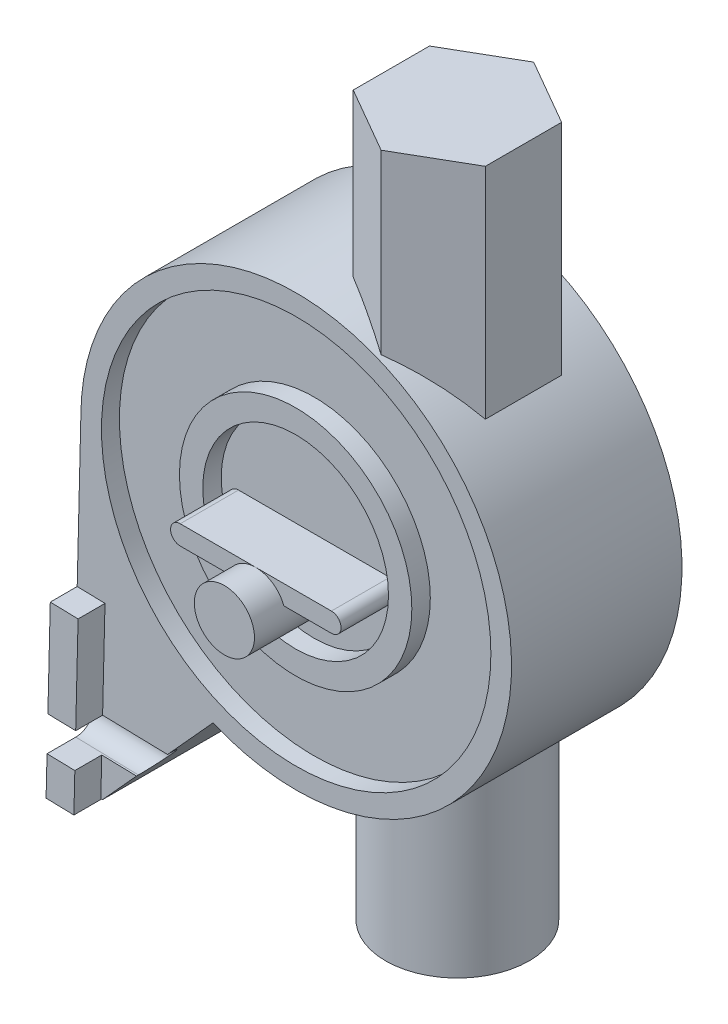
SolidWorks part; units mm, degrees
ref_plane "Front Plane" through (0, 0, 0) normal (0, 0, 1) x (1, 0, 0)
ref_plane "Top Plane" through (0, 0, 0) normal (0, 1, 0) x (1, 0, 0)
ref_plane "Right Plane" through (0, 0, 0) normal (1, 0, 0) x (0, 0, -1)
sketch "Sketch1" plane through (0, 0, 0) normal (0, 0, 1) x (1, 0, 0)
  line L0 (254.309, 185.0586) -> (255.9795, 135.0866) construction
  dimension "D1" = 50
sketch "Sketch3" plane through (0, 0, 0) normal (0, 0, 1) x (1, 0, 0)
  circle A0 centre (225, 142.5) radius 24
  dimension "D1" = 48
extrude "Boss-Extrude1" add sketch "Sketch3" along normal blind 19
sketch "Sketch5" plane through (0, 0, 0) normal (0, 0, 1) x (1, 0, 0)
  line L0 (201, 142.5) -> (200.1276, 106.7852)
  line L1 (200.1276, 106.7852) -> (203.4142, 106.7852)
  line L2 (203.4142, 106.7852) -> (215.7335, 120.3611)
  circle A0 centre (225, 142.5) radius 24 construction
  circle A3 centre (225, 142.5) radius 24
  arc A4 (201, 142.5) -> (215.7335, 120.3611) centre (225, 142.5) ccw
  dimension "D1" = 0
extrude "Boss-Extrude2" add sketch "Sketch5" along normal blind 19
ref_plane "Plane1" through (0, 0, 10) normal (0, 0, 1) x (1, 0, 0)
sketch "Sketch6" plane through (0, 0, 10) normal (0, 0, 1) x (1, 0, 0)
  line L0 (233.1699, 185.1714) -> (234.7697, 100.2588) construction
ref_axis "Axis1" through (233.1699, 185.1714, 10) along (0.0188, -0.9998, 0)
ref_plane "Plane2" through (0, 118.5, 0) normal (0, -1, 0) x (-1, 0, 0)
ref_plane "Plane3" through (0, 128.5, 0) normal (0, -1, 0) x (-1, 0, 0)
sketch "Sketch7" plane through (0, 128.5, 0) normal (0, -1, 0) x (-1, 0, 0)
  line L0 (3534.2774, -10) -> (-4002.217, -10) construction
  circle A0 centre (-233.9698, -10) radius 8
  dimension "D1" = 16
extrude "Boss-Extrude3" add sketch "Sketch7" along normal blind 22.5
ref_plane "Plane4" through (0, 158.5, 0) normal (0, -1, 0) x (-1, 0, 0)
sketch "Sketch8" plane through (0, 158.5, 0) normal (0, -1, 0) x (-1, 0, 0)
  line L0 (3534.2774, -10) -> (-4002.217, -10) construction
  line L1 (-241.331, -5.75) -> (-241.331, -14.25)
  line L2 (-241.331, -14.25) -> (-233.9698, -18.5)
  line L3 (-233.9698, -18.5) -> (-226.6086, -14.25)
  line L4 (-226.6086, -14.25) -> (-226.6086, -5.75)
  line L5 (-226.6086, -5.75) -> (-233.9698, -1.5)
  line L6 (-233.9698, -1.5) -> (-241.331, -5.75)
  circle A0 centre (-233.9698, -10) radius 7.3612 construction
extrude "Boss-Extrude4" add sketch "Sketch8" against normal blind 26
sketch "Sketch9" plane through (197.4015, -4.8217, 0) normal (-0.9997, 0.0244, 0) x (0, 0, 1)
  line L0 (0, 147.3657) -> (0, 111.6402) construction
  line L1 (19, 111.6402) -> (22, 111.6402)
  line L2 (19, 111.6402) -> (19, 130.8102)
  line L3 (19, 130.8102) -> (22, 130.8102)
  line L4 (22, 111.6402) -> (22, 130.8102)
  dimension "D1" = 22
  dimension "D2" = 19.17
extrude "Boss-Extrude5" add sketch "Sketch9" against normal blind 3.1
sketch "Sketch10" plane through (197.4015, -4.8217, 0) normal (-0.9997, 0.0244, 0) x (0, 0, 1)
  line L0 (5.15, 117.9352) -> (5.15, 122.2677) construction
  line L1 (16.85, 117.9352) -> (16.85, 122.2677) construction
  line L2 (11, 127.8393) -> (11, 106.4652) construction
  line L3 (0, 147.3657) -> (0, 111.6402) construction
  line L4 (22, 111.6402) -> (22, 130.8102) construction
  line L5 (3.205, 115.9902) -> (18.795, 115.9902) construction
  line L6 (19, 111.6402) -> (0, 111.6402) construction
  line L9 (0, 147.3657) -> (0, 111.6402)
  line L10 (0, 119.8802) -> (0, 115.9902)
  line L11 (3.205, 119.8802) -> (0, 119.8802)
  line L12 (22, 111.6402) -> (22, 130.8102)
  line L13 (22, 115.9902) -> (22, 119.8802)
  line L14 (3.205, 115.9902) -> (0, 115.9902)
  line L15 (18.795, 119.8802) -> (22, 119.8802)
  line L16 (18.795, 115.9902) -> (22, 115.9902)
  line L17 (1.46, 143.5702) -> (1.46, 162.4606) construction
  line L18 (4.82, 143.5702) -> (4.82, 151.263) construction
  line L19 (0, 171.9517) -> (0, 123.9517) construction
  line L21 (3.14, 141.8902) -> (22, 141.8902) construction
  arc A0 (3.205, 115.9902) -> (3.205, 119.8802) centre (3.205, 117.9352) ccw
  arc A1 (18.795, 119.8802) -> (18.795, 115.9902) centre (18.795, 117.9352) ccw
  circle A2 centre (3.14, 143.5702) radius 1.68
  dimension "D3" = 3.89
  dimension "D6" = 3.36
  dimension "D1" = 11.7
  dimension "D2" = 4.35
  dimension "D7" = 1.46
  dimension "D8" = 30.25
  dimension "D4" = 0
  dimension "D5" = 0
extrude "Cut-Extrude1" cut sketch "Sketch10" against normal blind 15
sketch "Sketch11" plane through (0, 0, 19) normal (0, 0, 1) x (1, 0, 0)
  line L0 (194.6129, 166.5) -> (247.7386, 166.5) construction
  line L1 (225, 164.2) -> (190.9337, 164.2) construction
  arc A0 (215.7335, 120.3611) -> (201, 142.5) centre (225, 142.5) ccw construction
  circle A1 centre (225, 142.5) radius 21.7
  point P0 (225, 142.5)
  point P1 (225, 142.5)
  dimension "D1" = 2.3
extrude "Cut-Extrude2" cut sketch "Sketch11" against normal blind 2
sketch "Sketch12" plane through (0, 0, 17) normal (0, 0, 1) x (1, 0, 0)
  circle A0 centre (225, 142.5) radius 21.7 construction
  circle A1 centre (225, 142.5) radius 10.35
  circle A2 centre (225, 142.5) radius 12.95
  point P0 (225, 142.5)
  dimension "D1" = 20.7
  dimension "D2" = 25.9
extrude "Boss-Extrude6" add sketch "Sketch12" along normal blind 2.06
sketch "Sketch13" plane through (0, 0, 17) normal (0, 0, 1) x (1, 0, 0)
  line L0 (225, 142.25) -> (241.9992, 142.25) construction
  line L1 (225, 129.55) -> (239.6517, 129.55) construction
  line L2 (225, 152.85) -> (225, 132.15) construction
  circle A0 centre (225, 138.9) radius 3.35
  circle A2 centre (225, 142.5) radius 12.95 construction
  circle A3 centre (225, 142.5) radius 12.95 construction
  circle A4 centre (225, 142.5) radius 10.35 construction
  point P15 (0, 0)
  dimension "D1" = 6.7
  dimension "D2" = 12.7
extrude "Boss-Extrude7" add sketch "Sketch13" along normal blind 10
sketch "Sketch14" plane through (0, 0, 17) normal (0, 0, 1) x (1, 0, 0)
  line L0 (225, 152.85) -> (225, 132.15) construction
  line L1 (216.575, 142.25) -> (233.425, 142.25) construction
  line L2 (222.8519, 142.25) -> (227.6896, 142.25) construction
  line L3 (215.5, 141.175) -> (215.5, 145.2165) construction
  line L4 (234.5, 141.175) -> (234.5, 144.9077) construction
  line L5 (216.575, 142.25) -> (233.425, 142.25)
  line L6 (216.575, 140.1) -> (233.425, 140.1)
  arc A0 (216.575, 142.25) -> (216.575, 140.1) centre (216.575, 141.175) ccw
  arc A1 (233.425, 140.1) -> (233.425, 142.25) centre (233.425, 141.175) ccw
  circle A2 centre (225, 142.5) radius 10.35 construction
  circle A3 centre (225, 142.5) radius 10.35 construction
  circle A4 centre (225, 138.9) radius 3.35 construction
  dimension "D1" = 2.15
  dimension "D2" = 19
extrude "Boss-Extrude8" add sketch "Sketch14" along normal blind 6.5
